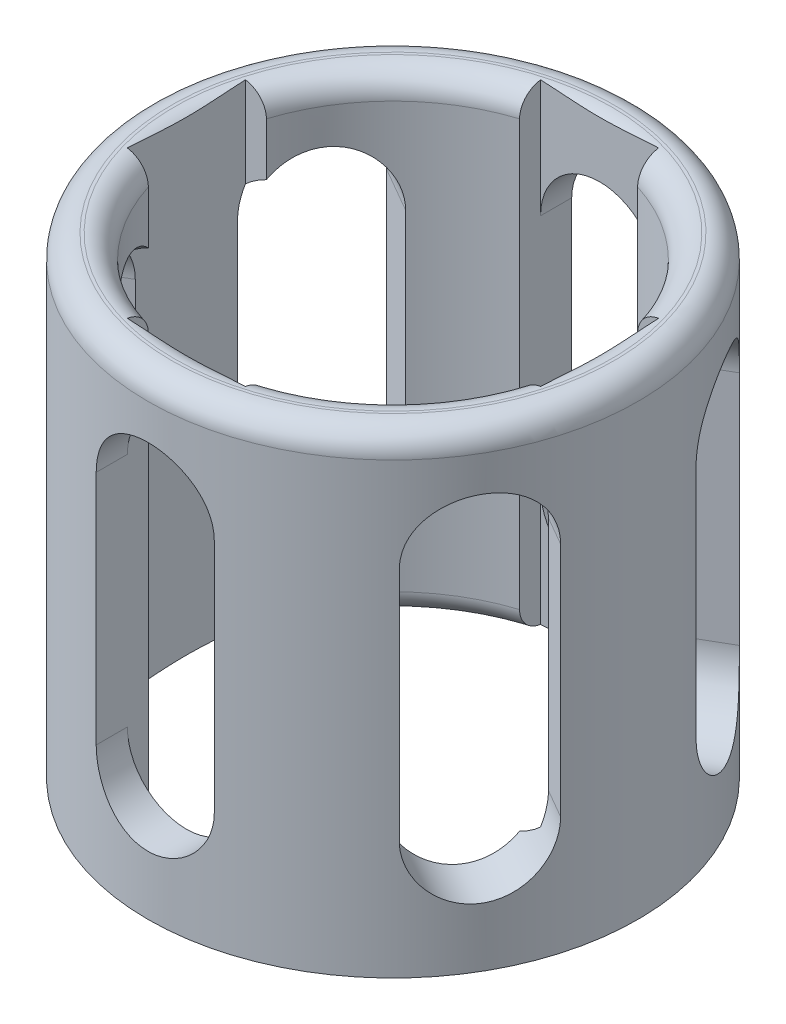
SolidWorks part; units mm, degrees
ref_plane "Front" through (0, 0, 0) normal (0, 0, 1) x (1, 0, 0)
ref_plane "Top" through (0, 0, 0) normal (0, 1, 0) x (1, 0, 0)
ref_plane "Right" through (0, 0, 0) normal (1, 0, 0) x (0, 0, -1)
sketch "Sketch1" plane through (0, 0, 0) normal (0, 1, 0) x (1, 0, 0)
  circle A0 centre (0, 0) radius 20.75
  circle A1 centre (0, 0) radius 16.5
  dimension "D1" = 41.5
  dimension "D2" = 33
extrude "Boss-Extrude1" add sketch "Sketch1" along normal blind 40
ref_plane "Plane1" through (0, 0, 20.75) normal (0, 0, 1) x (1, 0, 0)
sketch "Sketch2" plane through (0, 0, 20.75) normal (0, 0, 1) x (1, 0, 0)
  line L0 (0, 40) -> (0, 0) construction
  line L1 (20.75, 40) -> (-20.75, 40) construction
  line L2 (-20.75, 0) -> (20.75, 0) construction
  line L3 (-5, 20) -> (5, 20) construction
  line L4 (-5, 30) -> (5, 30)
  line L5 (-5, 30) -> (-5, 10)
  line L6 (-5, 10) -> (5, 10)
  line L7 (5, 30) -> (5, 10)
  line L8 (-5, 30) -> (5, 10) construction
  line L9 (-5, 10) -> (5, 30) construction
  arc A0 (-5, 30) -> (5, 30) centre (0, 30) cw
  arc A1 (-5, 10) -> (5, 10) centre (0, 10) ccw
  point P6 (0, 20)
  dimension "D1" = 10
  dimension "D2" = 20
extrude "Cut-Extrude1" cut sketch "Sketch2" against normal blind 20 contours L6 A1 | L7 L4 L5 L6 | A0 L4 region at (0, 32.1221, 20.75) region at (0, 20, 20.75) region at (0, 7.8779, 20.75)
pattern_circular "CirPattern1" count 6 over 360 about axis through (0, 40, 0) along (0, -1, 0) of "Cut-Extrude1"
fillet "Fillet1" radius 2 3 edges at (0, 40, 20.75) (0, 0, 16.5) (0, 40, 16.5)
sketch "Sketch3" plane through (0, 0, 0) normal (0, -1, 0) x (1, 0, 0)
  line L0 (0, 22.5626) -> (0, -27.9935) construction
  line L2 (-5, 17.5) -> (5, 17.5)
  line L3 (-5, 17.5) -> (-5, 15.5)
  line L4 (-5, 15.5) -> (5, 15.5)
  line L5 (5, 17.5) -> (5, 15.5)
  line L6 (-5, 17.5) -> (5, 15.5) construction
  line L7 (-5, 15.5) -> (5, 17.5) construction
  circle A0 centre (0, 0) radius 16.5 construction
  point P3 (0, 16.5)
  dimension "D1" = 10
  dimension "D2" = 2
extrude "Cut-Extrude2" cut sketch "Sketch3" against normal through all
ref_axis "Axis1" through (0, 38, 0) along (0, -1, 0)
pattern_circular "CirPattern2" count 4 over 360 about axis through (0, 38, 0) along (0, -1, 0) of "Cut-Extrude2"
